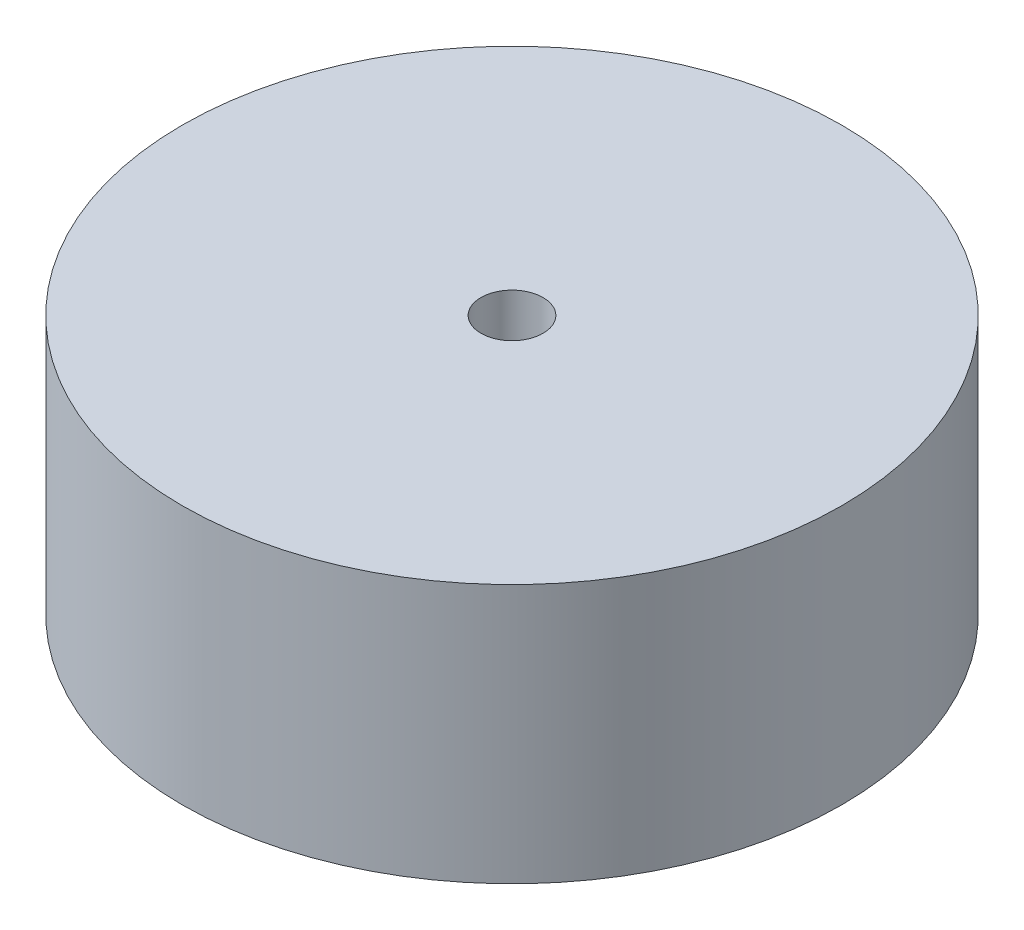
SolidWorks part; units mm, degrees
ref_plane "前基準面" through (0, 0, 0) normal (0, 0, 1) x (1, 0, 0)
ref_plane "上基準面" through (0, 0, 0) normal (0, 1, 0) x (1, 0, 0)
ref_plane "右基準面" through (0, 0, 0) normal (1, 0, 0) x (0, 0, -1)
sketch "草圖1" plane through (0, 0, 0) normal (0, 1, 0) x (1, 0, 0)
  circle A0 centre (0, 0) radius 42.5
  circle A1 centre (0, 0) radius 4
  dimension "D1" = 85
  dimension "D2" = 8
extrude "填料-伸長1" add sketch "草圖1" along normal blind 33.4
